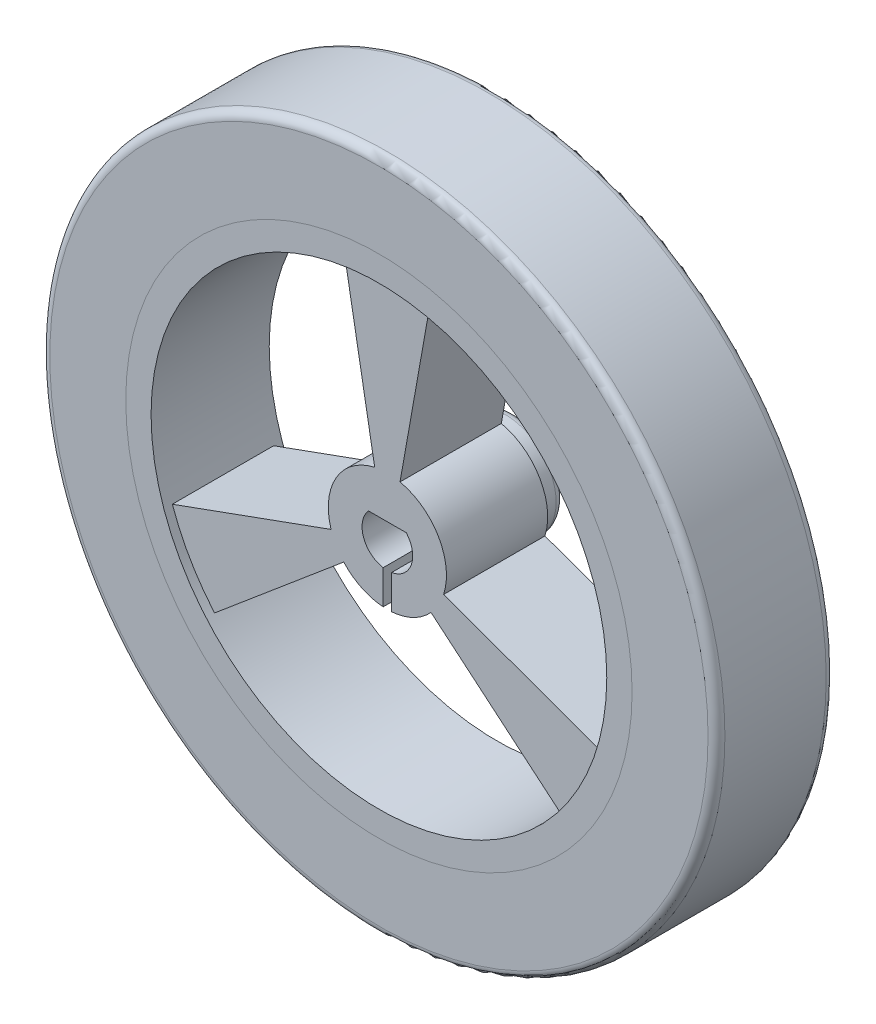
SolidWorks part; units mm, degrees
other "wheel"
other "tire"
ref_plane "Přední rovina" through (0, 0, 0) normal (0, 0, 1) x (1, 0, 0)
ref_plane "Horní rovina" through (0, 0, 0) normal (0, 1, 0) x (1, 0, 0)
ref_plane "Pravá rovina" through (0, 0, 0) normal (1, 0, 0) x (0, 0, -1)
sketch "Skica2" plane through (0, 0, 0) normal (1, 0, 0) x (0, 0, -1)
  line L0 (-3, 13.5) -> (-3, 0)
  line L1 (-2, 18) -> (2, 18)
  line L2 (2, 18) -> (2, 15)
  line L3 (2, 15) -> (3.5, 15)
  line L4 (3.5, 15) -> (3.5, 13.5)
  line L5 (3.5, 13.5) -> (3, 13.5)
  line L6 (4.5, 0) -> (-3, 0)
  line L7 (3, 13.5) -> (3, 3)
  line L8 (3, 3) -> (4, 3)
  line L9 (4.5, 2.5) -> (4.5, 0)
  line L10 (-36.9889, 0) -> (36.9889, 0) construction
  line L11 (0, 0) -> (0, 62.8313) construction
  line L13 (-3.5, 13.5) -> (-3, 13.5)
  line L14 (-3.5, 15) -> (-3.5, 13.5)
  line L15 (-2, 15) -> (-3.5, 15)
  line L16 (-2, 18) -> (-2, 15)
  arc A0 (4, 3) -> (4.5, 2.5) centre (4, 2.5) cw
  point P22 (0, 18)
  dimension "D9" = 0.5
  dimension "D1" = 36
  dimension "D2" = 7
  dimension "D3" = 3
  dimension "D4" = 6
  dimension "D5" = 1.5
  dimension "D6" = 6
  dimension "D7" = 8
  dimension "D8" = 1.5
revolve "Rotovat1" add sketch "Skica2" angle 360 about L10
sketch "Skica3" plane through (0, 0, 3) normal (0, 0, 1) x (1, 0, 0)
  line L0 (12.7391, -4.4682) -> (3.3357, -1.0598)
  line L1 (0, 0) -> (0, 29.5863) construction
  line L2 (-2.5, 13.2665) -> (-0.75, 3.4187)
  line L3 (10.2391, -8.7983) -> (2.5857, -2.3589)
  line L4 (-10.2391, -8.7983) -> (-2.5857, -2.3589)
  line L5 (-12.7391, -4.4682) -> (-3.3357, -1.0598)
  line L9 (2.5, 13.2665) -> (0.75, 3.4187)
  circle A0 centre (0, 0) radius 13.5 construction
  arc A1 (12.7391, -4.4682) -> (2.5, 13.2665) centre (0, 0) ccw
  arc A2 (-2.5, 13.2665) -> (-12.7391, -4.4682) centre (0, 0) ccw
  arc A3 (3.3357, -1.0598) -> (0.75, 3.4187) centre (0, 0) ccw
  arc A4 (-2.5857, -2.3589) -> (2.5857, -2.3589) centre (0, 0) ccw
  arc A5 (-10.2391, -8.7983) -> (10.2391, -8.7983) centre (0, 0) ccw
  arc A29 (-0.75, 3.4187) -> (-3.3357, -1.0598) centre (0, 0) ccw
  point P10 (-0.75, 3.4187)
  point P13 (0.75, 3.4187)
  dimension "D1" = 7
  dimension "D2" = 1.5
  dimension "D4" = 3
  dimension "D3" = 5
extrude "Odebrat vysunutím1" cut sketch "Skica3" against normal through all
sketch "Skica4" plane through (0, 0, 3) normal (0, 0, 1) x (1, 0, 0)
  line L0 (-1.118, 1) -> (1.118, 1)
  line L1 (0, 0) -> (0, -11.6723) construction
  line L2 (-0.25, -1.479) -> (-0.25, -4.8326)
  line L3 (0.25, -1.479) -> (0.25, -4.8326)
  line L4 (-0.25, -4.8326) -> (0.25, -4.8326)
  arc A0 (-1.118, 1) -> (-0.25, -1.479) centre (0, 0) ccw
  arc A1 (0.25, -1.479) -> (1.118, 1) centre (0, 0) ccw
  dimension "D1" = 3
  dimension "D2" = 2.5
  dimension "D3" = 0.5
extrude "Odebrat vysunutím2" cut sketch "Skica4" against normal through all
sketch "Skica5" plane through (0, 0, 0) normal (1, 0, 0) x (0, 0, -1)
  line L0 (-3.5, 15) -> (-3.5, 19.5)
  line L1 (-3, 20) -> (3, 20)
  line L2 (3.5, 19.5) -> (3.5, 15)
  line L3 (-2, 15) -> (-3.5, 15) construction
  line L4 (-2, 18) -> (-2, -18) construction
  line L5 (2, 18) -> (-2, 18) construction
  line L6 (2, -18) -> (2, 18) construction
  line L7 (3.5, 15) -> (2, 15) construction
  line L8 (-2, 15) -> (-3.5, 15)
  line L9 (-2, 18) -> (-2, 15)
  line L10 (2, 18) -> (-2, 18)
  line L11 (2, 15) -> (2, 18)
  line L12 (3.5, 15) -> (2, 15)
  line L13 (0, 0) -> (18.2922, 0) construction
  arc A0 (3, 20) -> (3.5, 19.5) centre (3, 19.5) cw
  arc A1 (-3.5, 19.5) -> (-3, 20) centre (-3, 19.5) cw
  dimension "D2" = 0.5
  dimension "D3" = 0.5
  dimension "D1" = 40
revolve "Rotovat2" add sketch "Skica5" angle 360 about L13
